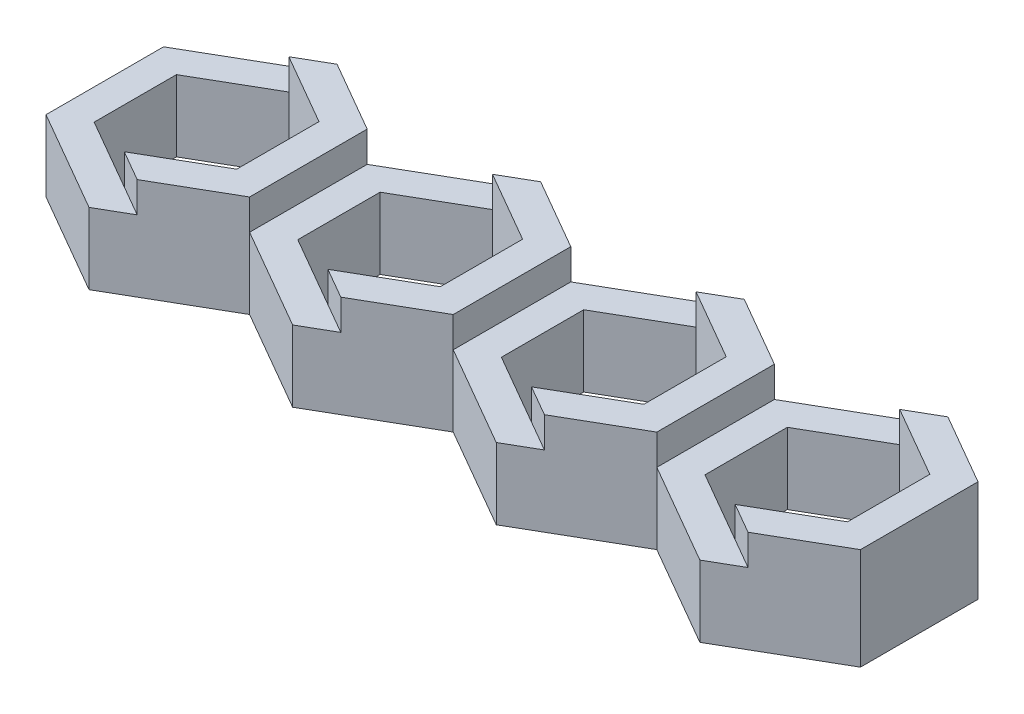
SolidWorks part; units mm, degrees
ref_plane "Front Plane" through (0, 0, 0) normal (0, 0, 1) x (1, 0, 0)
ref_plane "Top Plane" through (0, 0, 0) normal (0, 1, 0) x (1, 0, 0)
ref_plane "Right Plane" through (0, 0, 0) normal (1, 0, 0) x (0, 0, -1)
sketch "Sketch1" plane through (0, 0, 0) normal (0, 1, 0) x (1, 0, 0)
  line L0 (-45.1392, 13.7605) -> (54.8608, 13.7605)
  line L1 (-45.1392, -51.2395) -> (54.8608, -51.2395)
  line L2 (-45.1392, -51.2395) -> (-45.1392, 18.7605)
  line L3 (-45.1392, 18.7605) -> (54.8608, 18.7605)
  line L4 (54.8608, -51.2395) -> (54.8608, 18.7605)
  line L5 (-45.1392, -51.2395) -> (54.8608, 18.7605) construction
  line L6 (-45.1392, 18.7605) -> (54.8608, -51.2395) construction
  line L7 (-45.1392, -46.2395) -> (54.8608, -46.2395)
  line L8 (4.8608, -8.1566) -> (-2.1392, -12.1981)
  line L9 (4.8608, -4.6925) -> (-5.1392, -10.466)
  line L10 (-5.1392, -10.466) -> (-5.1392, -22.013)
  line L11 (-5.1392, -22.013) -> (4.8608, -27.7865)
  line L12 (4.8608, -27.7865) -> (14.8608, -22.013)
  line L13 (14.8608, -22.013) -> (14.8608, -10.466)
  line L14 (14.8608, -10.466) -> (4.8608, -4.6925)
  line L15 (-2.1392, -12.1981) -> (-2.1392, -20.281)
  line L16 (-2.1392, -20.281) -> (4.8608, -24.3224)
  line L17 (4.8608, -24.3224) -> (11.8608, -20.281)
  line L18 (11.8608, -20.281) -> (11.8608, -12.1981)
  line L19 (11.8608, -12.1981) -> (4.8608, -8.1566)
  line L20 (24.8608, -8.1566) -> (17.8608, -12.1981)
  line L21 (17.8608, -12.1981) -> (17.8608, -20.281)
  line L22 (17.8608, -20.281) -> (24.8608, -24.3224)
  line L23 (24.8608, -24.3224) -> (31.8608, -20.281)
  line L24 (31.8608, -20.281) -> (31.8608, -12.1981)
  line L25 (31.8608, -12.1981) -> (24.8608, -8.1566)
  line L26 (24.8608, -4.6925) -> (14.8608, -10.466)
  line L27 (14.8608, -10.466) -> (14.8608, -22.013)
  line L28 (14.8608, -22.013) -> (24.8608, -27.7865)
  line L29 (24.8608, -27.7865) -> (34.8608, -22.013)
  line L30 (34.8608, -22.013) -> (34.8608, -10.466)
  line L31 (34.8608, -10.466) -> (24.8608, -4.6925)
  line L32 (44.8608, -8.1566) -> (37.8608, -12.1981)
  line L33 (37.8608, -12.1981) -> (37.8608, -20.281)
  line L34 (37.8608, -20.281) -> (44.8608, -24.3224)
  line L35 (44.8608, -24.3224) -> (51.8608, -20.281)
  line L36 (51.8608, -20.281) -> (51.8608, -12.1981)
  line L37 (51.8608, -12.1981) -> (44.8608, -8.1566)
  line L38 (44.8608, -4.6925) -> (34.8608, -10.466)
  line L39 (34.8608, -10.466) -> (34.8608, -22.013)
  line L40 (34.8608, -22.013) -> (44.8608, -27.7865)
  line L41 (44.8608, -27.7865) -> (54.8608, -22.013)
  line L42 (54.8608, -22.013) -> (54.8608, -10.466)
  line L43 (54.8608, -10.466) -> (44.8608, -4.6925)
  line L44 (-15.1392, -8.1566) -> (-22.1392, -12.1981)
  line L45 (-22.1392, -12.1981) -> (-22.1392, -20.281)
  line L46 (-22.1392, -20.281) -> (-15.1392, -24.3224)
  line L47 (-15.1392, -24.3224) -> (-8.1392, -20.281)
  line L48 (-8.1392, -20.281) -> (-8.1392, -12.1981)
  line L49 (-8.1392, -12.1981) -> (-15.1392, -8.1566)
  line L50 (-15.1392, -4.6925) -> (-25.1392, -10.466)
  line L51 (-25.1392, -10.466) -> (-25.1392, -22.013)
  line L52 (-25.1392, -22.013) -> (-15.1392, -27.7865)
  line L53 (-15.1392, -27.7865) -> (-5.1392, -22.013)
  line L54 (-5.1392, -22.013) -> (-5.1392, -10.466)
  line L55 (-5.1392, -10.466) -> (-15.1392, -4.6925)
  line L56 (-35.1392, -8.1566) -> (-42.1392, -12.1981)
  line L57 (-42.1392, -12.1981) -> (-42.1392, -20.281)
  line L58 (-42.1392, -20.281) -> (-35.1392, -24.3224)
  line L59 (-35.1392, -24.3224) -> (-28.1392, -20.281)
  line L60 (-28.1392, -20.281) -> (-28.1392, -12.1981)
  line L61 (-28.1392, -12.1981) -> (-35.1392, -8.1566)
  line L62 (-35.1392, -4.6925) -> (-45.1392, -10.466)
  line L63 (-45.1392, -10.466) -> (-45.1392, -22.013)
  line L64 (-45.1392, -22.013) -> (-35.1392, -27.7865)
  line L65 (-35.1392, -27.7865) -> (-25.1392, -22.013)
  line L66 (-25.1392, -22.013) -> (-25.1392, -10.466)
  line L67 (-25.1392, -10.466) -> (-35.1392, -4.6925)
  line L68 (24.8608, 11.4733) -> (17.8608, 7.4318)
  line L69 (17.8608, 7.4318) -> (17.8608, -0.6511)
  line L70 (17.8608, -0.6511) -> (24.8608, -4.6925)
  line L71 (24.8608, -4.6925) -> (31.8608, -0.6511)
  line L72 (31.8608, -0.6511) -> (31.8608, 7.4318)
  line L73 (31.8608, 7.4318) -> (24.8608, 11.4733)
  line L74 (22.8223, 13.7605) -> (14.8608, 9.1639)
  line L75 (14.8608, 9.1639) -> (14.8608, -2.3831)
  line L76 (14.8608, -2.3831) -> (24.8608, -8.1566)
  line L77 (24.8608, -8.1566) -> (34.8608, -2.3831)
  line L78 (34.8608, -2.3831) -> (34.8608, 9.1639)
  line L79 (34.8608, 9.1639) -> (26.8993, 13.7605)
  line L80 (2.8223, 13.7605) -> (-5.1392, 9.1639)
  line L81 (-5.1392, 9.1639) -> (-5.1392, -2.3831)
  line L82 (-5.1392, -2.3831) -> (4.8608, -8.1566)
  line L83 (4.8608, -8.1566) -> (14.8608, -2.3831)
  line L84 (14.8608, -2.3831) -> (14.8608, 9.1639)
  line L85 (14.8608, 9.1639) -> (6.8993, 13.7605)
  line L86 (4.8608, 11.4733) -> (-2.1392, 7.4318)
  line L87 (-2.1392, 7.4318) -> (-2.1392, -0.6511)
  line L88 (-2.1392, -0.6511) -> (4.8608, -4.6925)
  line L89 (4.8608, -4.6925) -> (11.8608, -0.6511)
  line L90 (11.8608, -0.6511) -> (11.8608, 7.4318)
  line L91 (11.8608, 7.4318) -> (4.8608, 11.4733)
  line L92 (-17.1777, 13.7605) -> (-25.1392, 9.1639)
  line L93 (-25.1392, 9.1639) -> (-25.1392, -2.3831)
  line L94 (-25.1392, -2.3831) -> (-15.1392, -8.1566)
  line L95 (-15.1392, -8.1566) -> (-5.1392, -2.3831)
  line L96 (-5.1392, -2.3831) -> (-5.1392, 9.1639)
  line L97 (-5.1392, 9.1639) -> (-13.1007, 13.7605)
  line L98 (-15.1392, 11.4733) -> (-22.1392, 7.4318)
  line L99 (-22.1392, 7.4318) -> (-22.1392, -0.6511)
  line L100 (-22.1392, -0.6511) -> (-15.1392, -4.6925)
  line L101 (-15.1392, -4.6925) -> (-8.1392, -0.6511)
  line L102 (-8.1392, -0.6511) -> (-8.1392, 7.4318)
  line L103 (-8.1392, 7.4318) -> (-15.1392, 11.4733)
  line L104 (-37.1777, 13.7605) -> (-45.1392, 9.1639)
  line L105 (-45.1392, 9.1639) -> (-45.1392, -2.3831)
  line L106 (-45.1392, -2.3831) -> (-35.1392, -8.1566)
  line L107 (-35.1392, -8.1566) -> (-25.1392, -2.3831)
  line L108 (-25.1392, -2.3831) -> (-25.1392, 9.1639)
  line L109 (-25.1392, 9.1639) -> (-33.1007, 13.7605)
  line L110 (-35.1392, 11.4733) -> (-42.1392, 7.4318)
  line L111 (-42.1392, 7.4318) -> (-42.1392, -0.6511)
  line L112 (-42.1392, -0.6511) -> (-35.1392, -4.6925)
  line L113 (-35.1392, -4.6925) -> (-28.1392, -0.6511)
  line L114 (-28.1392, -0.6511) -> (-28.1392, 7.4318)
  line L115 (-28.1392, 7.4318) -> (-35.1392, 11.4733)
  line L116 (42.8223, 13.7605) -> (34.8608, 9.1639)
  line L117 (34.8608, 9.1639) -> (34.8608, -2.3831)
  line L118 (34.8608, -2.3831) -> (44.8608, -8.1566)
  line L119 (44.8608, -8.1566) -> (54.8608, -2.3831)
  line L120 (54.8608, -2.3831) -> (54.8608, 9.1639)
  line L121 (54.8608, 9.1639) -> (46.8993, 13.7605)
  line L122 (44.8608, 11.4733) -> (37.8608, 7.4318)
  line L123 (37.8608, 7.4318) -> (37.8608, -0.6511)
  line L124 (37.8608, -0.6511) -> (44.8608, -4.6925)
  line L125 (44.8608, -4.6925) -> (51.8608, -0.6511)
  line L126 (51.8608, -0.6511) -> (51.8608, 7.4318)
  line L127 (51.8608, 7.4318) -> (44.8608, 11.4733)
  line L128 (-35.1392, -27.7865) -> (-42.1392, -31.828)
  line L129 (-42.1392, -31.828) -> (-42.1392, -39.9109)
  line L130 (-42.1392, -39.9109) -> (-35.1392, -43.9523)
  line L131 (-35.1392, -43.9523) -> (-28.1392, -39.9109)
  line L132 (-28.1392, -39.9109) -> (-28.1392, -31.828)
  line L133 (-28.1392, -31.828) -> (-35.1392, -27.7865)
  line L134 (-35.1392, -24.3224) -> (-45.1392, -30.0959)
  line L135 (-45.1392, -30.0959) -> (-45.1392, -41.6429)
  line L136 (-45.1392, -41.6429) -> (-37.1777, -46.2395)
  line L137 (-33.1007, -46.2395) -> (-25.1392, -41.6429)
  line L138 (-25.1392, -41.6429) -> (-25.1392, -30.0959)
  line L139 (-25.1392, -30.0959) -> (-35.1392, -24.3224)
  line L140 (-15.1392, -27.7865) -> (-22.1392, -31.828)
  line L141 (-22.1392, -31.828) -> (-22.1392, -39.9109)
  line L142 (-22.1392, -39.9109) -> (-15.1392, -43.9523)
  line L143 (-15.1392, -43.9523) -> (-8.1392, -39.9109)
  line L144 (-8.1392, -39.9109) -> (-8.1392, -31.828)
  line L145 (-8.1392, -31.828) -> (-15.1392, -27.7865)
  line L146 (-15.1392, -24.3224) -> (-25.1392, -30.0959)
  line L147 (-25.1392, -30.0959) -> (-25.1392, -41.6429)
  line L148 (-25.1392, -41.6429) -> (-17.1777, -46.2395)
  line L149 (-13.1007, -46.2395) -> (-5.1392, -41.6429)
  line L150 (-5.1392, -41.6429) -> (-5.1392, -30.0959)
  line L151 (-5.1392, -30.0959) -> (-15.1392, -24.3224)
  line L152 (4.8608, -27.7865) -> (-2.1392, -31.828)
  line L153 (-2.1392, -31.828) -> (-2.1392, -39.9109)
  line L154 (-2.1392, -39.9109) -> (4.8608, -43.9523)
  line L155 (4.8608, -43.9523) -> (11.8608, -39.9109)
  line L156 (11.8608, -39.9109) -> (11.8608, -31.828)
  line L157 (11.8608, -31.828) -> (4.8608, -27.7865)
  line L158 (4.8608, -24.3224) -> (-5.1392, -30.0959)
  line L159 (-5.1392, -30.0959) -> (-5.1392, -41.6429)
  line L160 (-5.1392, -41.6429) -> (2.8223, -46.2395)
  line L161 (6.8993, -46.2395) -> (14.8608, -41.6429)
  line L162 (14.8608, -41.6429) -> (14.8608, -30.0959)
  line L163 (14.8608, -30.0959) -> (4.8608, -24.3224)
  line L164 (24.8608, -27.7865) -> (17.8608, -31.828)
  line L165 (17.8608, -31.828) -> (17.8608, -39.9109)
  line L166 (17.8608, -39.9109) -> (24.8608, -43.9523)
  line L167 (24.8608, -43.9523) -> (31.8608, -39.9109)
  line L168 (31.8608, -39.9109) -> (31.8608, -31.828)
  line L169 (31.8608, -31.828) -> (24.8608, -27.7865)
  line L170 (24.8608, -24.3224) -> (14.8608, -30.0959)
  line L171 (14.8608, -30.0959) -> (14.8608, -41.6429)
  line L172 (14.8608, -41.6429) -> (22.8223, -46.2395)
  line L173 (26.8993, -46.2395) -> (34.8608, -41.6429)
  line L174 (34.8608, -41.6429) -> (34.8608, -30.0959)
  line L175 (34.8608, -30.0959) -> (24.8608, -24.3224)
  line L176 (44.8608, -27.7865) -> (37.8608, -31.828)
  line L177 (37.8608, -31.828) -> (37.8608, -39.9109)
  line L178 (37.8608, -39.9109) -> (44.8608, -43.9523)
  line L179 (44.8608, -43.9523) -> (51.8608, -39.9109)
  line L180 (51.8608, -39.9109) -> (51.8608, -31.828)
  line L181 (51.8608, -31.828) -> (44.8608, -27.7865)
  line L182 (44.8608, -24.3224) -> (34.8608, -30.0959)
  line L183 (34.8608, -30.0959) -> (34.8608, -41.6429)
  line L184 (34.8608, -41.6429) -> (42.8223, -46.2395)
  line L185 (46.8993, -46.2395) -> (54.8608, -41.6429)
  line L186 (54.8608, -41.6429) -> (54.8608, -30.0959)
  line L187 (54.8608, -30.0959) -> (44.8608, -24.3224)
  line L188 (-35.1392, 13.7605) -> (-35.1392, -4.6925)
  line L189 (-15.1392, 13.7605) -> (-15.1392, -4.6925)
  line L190 (4.8608, 13.7605) -> (4.8608, -4.6925)
  line L191 (24.8608, 13.7605) -> (24.8608, -4.6925)
  line L192 (44.8608, 13.7605) -> (44.8608, -4.6925)
  line L193 (44.8608, -27.7865) -> (44.8608, -46.2395)
  line L194 (24.8608, -27.7865) -> (24.8608, -46.2395)
  line L195 (4.8608, -27.7865) -> (4.8608, -46.2395)
  line L196 (4.8608, -8.1566) -> (4.8608, -24.3224)
  line L197 (-15.1392, -8.1566) -> (-15.1392, -24.3224)
  line L198 (-35.1392, -8.1566) -> (-35.1392, -24.3224)
  line L199 (-35.1392, -27.7865) -> (-35.1392, -46.2395)
  line L200 (-15.1392, -27.7865) -> (-15.1392, -46.2395)
  line L201 (44.8608, -8.1566) -> (44.8608, -24.3224)
  line L202 (24.8608, -8.1566) -> (24.8608, -24.3224)
  circle A0 centre (4.8608, -16.2395) radius 10 construction
  point P0 (4.8608, -16.2395)
  dimension "D3" = 46.8993
  dimension "D1" = 10
  dimension "D2" = 3
  dimension "D4" = 18.7605
extrude "Boss-Extrude3" add sketch "Sketch1" along normal blind 10 contours L151 L53 L10 L55 L95 L49 L48 L47 | L163 L12 L13 L14 L83 L19 L18 L17 | L175 L29 L30 L31 L77 L25 L24 L23 | L187 L41 L4 L43 L119 L37 L36 L35 region at (54.6405, 0, 16.2395) region at (-13.529, 0, 7.4814) region at (31.2507, 0, 8.6361) region at (6.471, 0, 7.4814)
extrude "Boss-Extrude4" add sketch "Sketch1<8>" along normal blind 7 contours L53 L151 L146 L52 | L146 L46 L45 L44 L94 L50 L51 L52 | L94 L95 L55 L50 | L82 L83 L14 L9 | L158 L16 L15 L8 L82 L9 L10 L11 | L12 L163 L158 L11 | L29 L175 L170 L28 | L170 L22 L21 L20 L76 L26 L13 L28 | L76 L77 L31 L26 | L118 L119 L43 L38 | L182 L34 L33 L32 L118 L38 L30 L40 | L41 L187 L182 L40 region at (-16.7493, 0, 7.4814) region at (-15.1392, 0, 6.4246) region at (44.8608, 0, 6.4246) region at (41.2507, 0, 9.9866) region at (-15.1392, 0, 26.0545) region at (44.8608, 0, 26.0545) region at (3.2507, 0, 7.4814) region at (4.8608, 0, 6.4246) region at (24.8608, 0, 6.4246) region at (21.2507, 0, 9.9866) region at (4.8608, 0, 26.0545) region at (24.8608, 0, 26.0545)
sketch "Sketch1<8>" plane through (0, 0, 0) normal (0, 1, 0) x (1, 0, 0) same geometry as "Sketch1"
